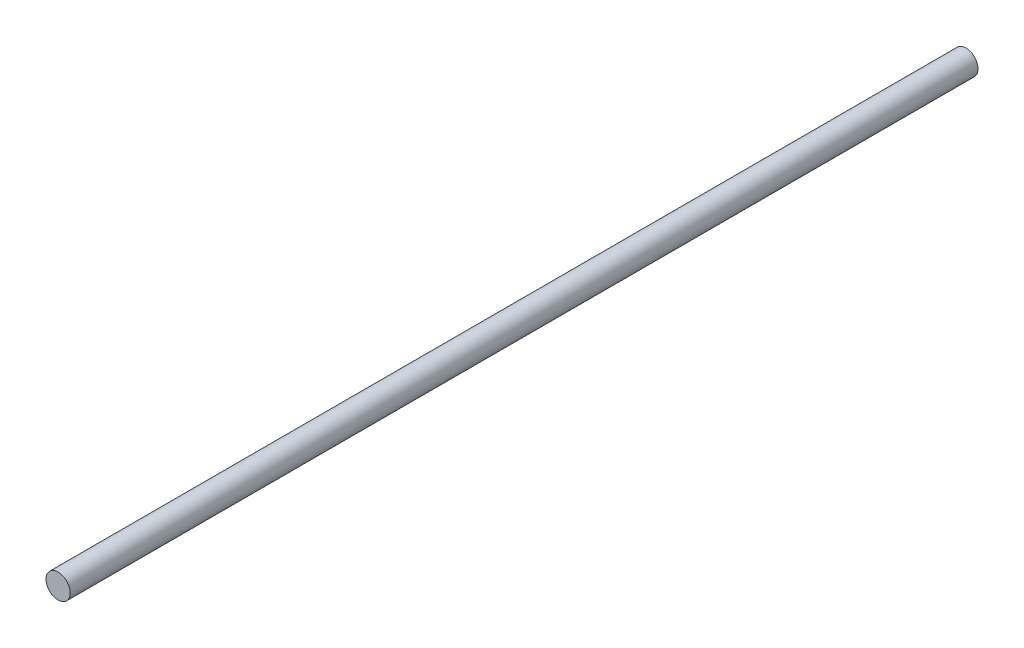
SolidWorks part; units mm, degrees
ref_plane "Front Plane" through (0, 0, 0) normal (0, 0, 1) x (1, 0, 0)
ref_plane "Top Plane" through (0, 0, 0) normal (0, 1, 0) x (1, 0, 0)
ref_plane "Right Plane" through (0, 0, 0) normal (1, 0, 0) x (0, 0, -1)
sketch "Sketch1" plane through (0, 0, 0) normal (0, 0, 1) x (1, 0, 0)
  circle A0 centre (0, 0) radius 1
extrude "Boss-Extrude1" add sketch "Sketch1" along normal blind 75 contours A0
